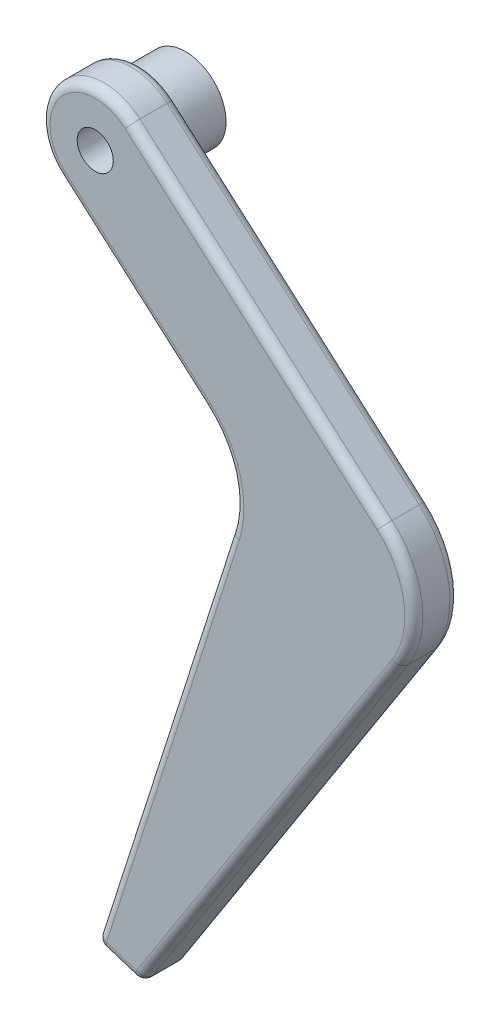
SolidWorks part; units mm, degrees
ref_plane "Front Plane" through (0, 0, 0) normal (0, 0, 1) x (1, 0, 0)
ref_plane "Top Plane" through (0, 0, 0) normal (0, 1, 0) x (1, 0, 0)
ref_plane "Right Plane" through (0, 0, 0) normal (1, 0, 0) x (0, 0, -1)
sketch "Sketch2" plane through (0, 0, 0) normal (0, 0, 1) x (1, 0, 0)
  line L1 (-10, -126) -> (-5, -127.6015)
  line L2 (-5, -127.6015) -> (23.7174, -82.9723)
  line L3 (-10, -126) -> (5.0018, -79.1624)
  line L4 (2.0789, -68.5999) -> (-13.9603, -54.5073)
  line L5 (-6.0397, -45.4927) -> (21.9085, -70.0488)
  arc A0 (-6.0397, -45.4927) -> (-13.9603, -54.5073) centre (-10, -50) ccw
  circle A1 centre (-10, -50) radius 2
  arc A3 (2.0789, -68.5999) -> (5.0018, -79.1624) centre (-4.5216, -76.1121) cw
  arc A4 (23.7174, -82.9723) -> (21.9085, -70.0488) centre (15.308, -77.5611) ccw
extrude "Boss-Extrude1" add sketch "Sketch2" along normal mid plane 5
fillet "Fillet1" radius 1 18 edges at (9.3587, -105.2869, -2.5) (25.2114, -76.1748, -2.5) (7.9344, -57.7707, -2.5) (-14.5073, -46.0397, -2.5) (-5.9407, -61.5536, -2.5) (5.1162, -73.445, -2.5) (9.3587, -105.2869, 2.5) (25.2114, -76.1748, 2.5) (7.9344, -57.7707, 2.5) (-14.5073, -46.0397, 2.5) (-2.4991, -102.5812, 2.5) (5.1162, -73.445, 2.5) (-7.5, -126.8007, -2.5) (-5, -127.6015, 0) (-7.5, -126.8007, 2.5) (-10, -126, 0) (-2.4991, -102.5812, -2.5) (-5.9407, -61.5536, 2.5)
sketch "Sketch3" plane through (0, 0, -2.5) normal (0, 0, -1) x (-1, 0, 0)
  circle A0 centre (10, -50) radius 4.5
extrude "Boss-Extrude2" add sketch "Sketch3" along normal blind 5
sketch "Sketch4" plane through (0, 0, -7.5) normal (0, 0, -1) x (-1, 0, 0)
  circle A0 centre (10, -50) radius 2.5
extrude "Cut-Extrude1" cut sketch "Sketch4" against normal blind 3
sketch "Sketch5" plane through (0, 0, -2.5) normal (0, 0, 1) x (1, 0, 0)
  circle A0 centre (-10, -50) radius 1
extrude "Cut-Extrude2" cut sketch "Sketch5" against normal up to surface (5 mm away) up to face at (-12.5, -50, -7.5)
